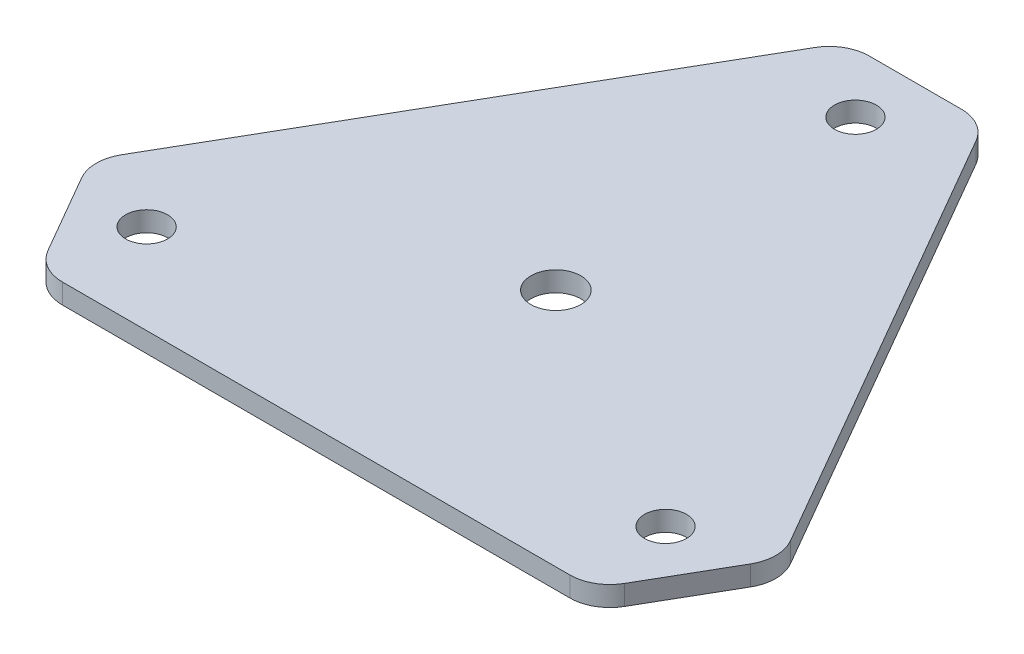
SolidWorks part; units mm, degrees
material "Thornel Mat VMA"
ref_plane "Front Plane" through (0, 0, 0) normal (0, 0, 1) x (1, 0, 0)
ref_plane "Top Plane" through (0, 0, 0) normal (0, 1, 0) x (1, 0, 0)
ref_plane "Right Plane" through (0, 0, 0) normal (1, 0, 0) x (0, 0, -1)
sketch "Sketch1" plane through (0, 0, 0) normal (0, 1, 0) x (1, 0, 0)
  line L0 (6.7849, 23.0936) -> (3.3349, 17.1181)
  line L1 (21.8849, 49.2476) -> (25.3349, 55.2232)
  line L2 (48.3541, 49.2476) -> (44.9041, 55.2232)
  line L3 (66.9041, 17.1181) -> (63.4541, 23.0936)
  line L4 (57.1195, 0.1706) -> (50.2195, 0.1706)
  line L5 (50.2195, 0.1706) -> (50.315, 0.1318)
  line L6 (20.0195, 0.1706) -> (13.1195, 0.1706)
  line L7 (30.317, 60.1706) -> (28.1913, 60.1706)
  line L8 (28.1913, 60.1706) -> (26.3349, 56.9552)
  line L9 (39.9221, 60.1706) -> (42.0477, 60.1706)
  line L10 (42.0477, 60.1706) -> (43.9041, 56.9552)
  line L11 (67.9041, 15.386) -> (69.7605, 12.1706)
  line L12 (69.7605, 12.1706) -> (68.6977, 10.3297)
  line L13 (63.8952, 2.0115) -> (62.8323, 0.1706)
  line L14 (62.8323, 0.1706) -> (59.1195, 0.1706)
  line L15 (11.1195, 0.1706) -> (7.4067, 0.1706)
  line L16 (7.4067, 0.1706) -> (6.3439, 2.0115)
  line L17 (1.5413, 10.3297) -> (0.4785, 12.1706)
  line L18 (0.4785, 12.1706) -> (2.3349, 15.386)
  line L19 (39.9221, 60.1706) -> (30.317, 60.1706)
  line L20 (26.3349, 56.9552) -> (25.3349, 55.2232)
  line L21 (21.8849, 49.2476) -> (6.7849, 23.0936)
  line L22 (3.3349, 17.1181) -> (2.3349, 15.386)
  line L23 (1.5413, 10.3297) -> (6.3439, 2.0115)
  line L24 (11.1195, 0.1706) -> (13.1195, 0.1706)
  line L25 (20.0195, 0.1706) -> (50.2195, 0.1706)
  line L26 (57.1195, 0.1706) -> (59.1195, 0.1706)
  line L27 (63.8952, 2.0115) -> (68.6977, 10.3297)
  line L28 (67.9041, 15.386) -> (66.9041, 17.1181)
  line L29 (63.4541, 23.0936) -> (48.3541, 49.2476)
  line L30 (44.9041, 55.2232) -> (43.9041, 56.9552)
  line L31 (0, 0) -> (101.9352, 0) construction
  line L32 (0, 0) -> (0, 87.2821) construction
extrude "Boss-Extrude1" add sketch "Sketch1" along normal blind 2 contours L2 L30 L10 L9 L19 L7 L8 L20 L1 L21 L0 L22 L18 L17 L23 L16 L15 L24 L6 L25 L4 L26 L14 L13 L27 L12 L11 L28 L3 L29 region at (35.1195, 0, -24.1706)
sketch "Sketch3" plane through (0, 2, 0) normal (0, 1, 0) x (1, 0, 0)
  line L0 (14.3349, 36.1706) -> (35.1195, 24.1706) construction
  line L2 (35.1195, 0.1706) -> (35.1195, 24.1706) construction
  line L3 (28.1913, 60.1706) -> (0.4785, 12.1706) construction
  line L5 (55.9041, 36.1706) -> (35.1195, 24.1706) construction
  line L7 (69.7605, 12.1706) -> (42.0477, 60.1706) construction
  line L8 (62.8323, 0.1706) -> (7.4067, 0.1706) construction
sketch "Sketch4" plane through (0, 2, 0) normal (0, 1, 0) x (1, 0, 0)
  line L0 (35.1195, 24.1706) -> (35.1195, 54.1706) construction
  line L1 (35.1195, 24.1706) -> (9.1388, 9.1706) construction
  line L2 (35.1195, 24.1706) -> (61.1003, 9.1706) construction
  circle A0 centre (35.1195, 24.1706) radius 30 construction
  circle A1 centre (35.1195, 54.1706) radius 2.1
  circle A2 centre (9.1388, 9.1706) radius 2.1
  circle A3 centre (61.1003, 9.1706) radius 2.1
  dimension "D1" = 60
  dimension "D4" = 4.2
  dimension "D2" = 120
  dimension "D3" = 120
extrude "Cut-Extrude1" cut sketch "Sketch4" against normal through all
sketch "Sketch5" plane through (0, 2, 0) normal (0, 1, 0) x (1, 0, 0)
  circle A0 centre (35.1195, 24.1706) radius 2.5
  dimension "D1" = 5
extrude "Cut-Extrude2" cut sketch "Sketch5" against normal through all
fillet "Fillet1" radius 4 6 edges at (69.7605, 1, -12.1706) (62.8323, 1, -0.1706) (7.4067, 1, -0.1706) (0.4785, 1, -12.1706) (28.1913, 1, -60.1706) (42.0477, 1, -60.1706)
